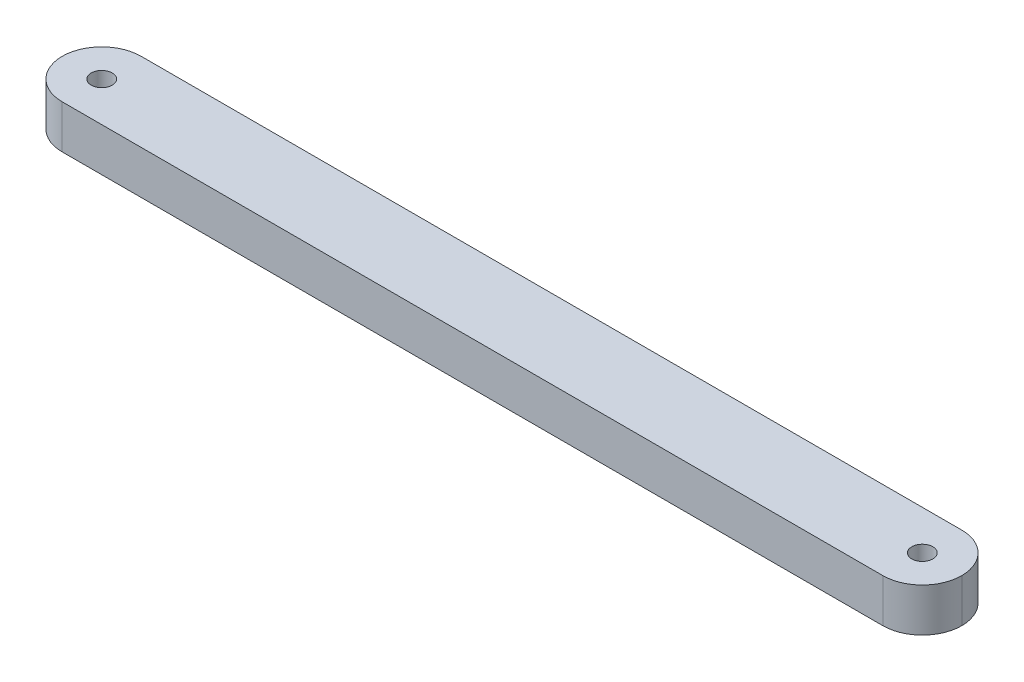
SolidWorks part; units mm, degrees
ref_plane "Front Plane" through (0, 0, 0) normal (0, 0, 1) x (1, 0, 0)
ref_plane "Top Plane" through (0, 0, 0) normal (0, 1, 0) x (1, 0, 0)
ref_plane "Right Plane" through (0, 0, 0) normal (1, 0, 0) x (0, 0, -1)
sketch "Sketch1" plane through (0, 0, 0) normal (0, 1, 0) x (1, 0, 0)
  line L0 (-66.04, 0) -> (0, 0) construction
  line L1 (-72.39, -6.35) -> (72.39, -6.35) construction
  line L2 (-72.39, -6.35) -> (-72.39, 6.35)
  line L3 (-72.39, 6.35) -> (72.39, 6.35)
  line L4 (72.39, -6.35) -> (72.39, 6.35)
  line L5 (-72.39, -6.35) -> (72.39, 6.35) construction
  line L6 (-72.39, 6.35) -> (72.39, -6.35) construction
  line L7 (0, 6.35) -> (0, -6.35) construction
  line L8 (-6.35, -31.75) -> (-6.35, 6.35) construction
  line L9 (-6.35, -31.75) -> (6.35, -31.75)
  line L10 (-6.35, 6.35) -> (6.35, 6.35)
  line L11 (6.35, -31.75) -> (6.35, 6.35) construction
  line L12 (-6.35, -31.75) -> (6.35, 6.35) construction
  line L13 (-6.35, 6.35) -> (6.35, -31.75) construction
  line L14 (-72.39, -6.35) -> (-6.35, -6.35)
  line L15 (-6.35, -6.35) -> (-6.35, -31.75)
  line L16 (6.35, -31.75) -> (6.35, -6.35)
  line L17 (6.35, -6.35) -> (72.39, -6.35)
  line L18 (-6.35, -6.35) -> (6.35, -6.35)
  circle A0 centre (-66.04, 0) radius 1.7
  circle A1 centre (66.04, 0) radius 1.7
  circle A2 centre (0, -25.4) radius 1.7
  point P0 (0, 0)
  point P13 (0, -12.7)
  point P22 (0, -31.75)
  dimension "D5" = 12.7
  dimension "D6" = 38.1
  dimension "D3" = 6.35
  dimension "D4" = 3.4
  dimension "D7" = 6.35
  dimension "D1" = 144.78
  dimension "D2" = 12.7
extrude "Boss-Extrude1" add sketch "Sketch1" along normal blind 6.985 contours L16 L17 L4 L3 L2 L14 L15 L9 A2 A0 A1 region at (0, 0, 0)
fillet "Fillet1" radius 6.35 4 edges at (72.39, 3.4925, -6.35) (-72.39, 3.4925, -6.35) (-72.39, 3.4925, 6.35) (72.39, 3.4925, 6.35)
